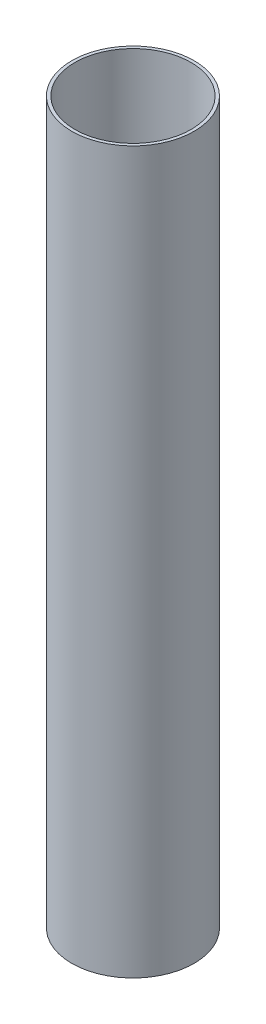
SolidWorks part; units mm, degrees
material "S-Glass Fiber"
ref_plane "Front Plane" through (0, 0, 0) normal (0, 0, 1) x (1, 0, 0)
ref_plane "Top Plane" through (0, 0, 0) normal (0, 1, 0) x (1, 0, 0)
ref_plane "Right Plane" through (0, 0, 0) normal (1, 0, 0) x (0, 0, -1)
sketch "Sketch1" plane through (0, 0, 0) normal (0, 1, 0) x (1, 0, 0)
  circle A0 centre (0, 0) radius 32.258
  circle A1 centre (0, 0) radius 33.9725
  dimension "D1" = 64.516
  dimension "D2" = 67.945
extrude "Boss-Extrude1" add sketch "Sketch1" along normal blind 400
ref_plane "Plane1" through (0, 0, 0) normal (-0.7071, 0, 0.7071) x (0.7071, 0, 0.7071)
sketch "Sketch2" plane through (0, 0, 0) normal (-0.7071, 0, 0.7071) x (0.7071, 0, 0.7071)
  line L2 (0, 179) -> (-33.9725, 179)
  line L3 (0, 179) -> (0, 139)
  line L4 (0, 139) -> (-33.9725, 139)
  line L5 (-33.9725, 179) -> (-33.9725, 139)
  point P7 (-33.9725, 137.6568)
  point P8 (0, 0)
  dimension "D1" = 40
  dimension "D2" = 139
revolve "UMBILICAL CONNECTOR PASSTHRU" cut sketch "Sketch2" angle 20 mid plane about L3
